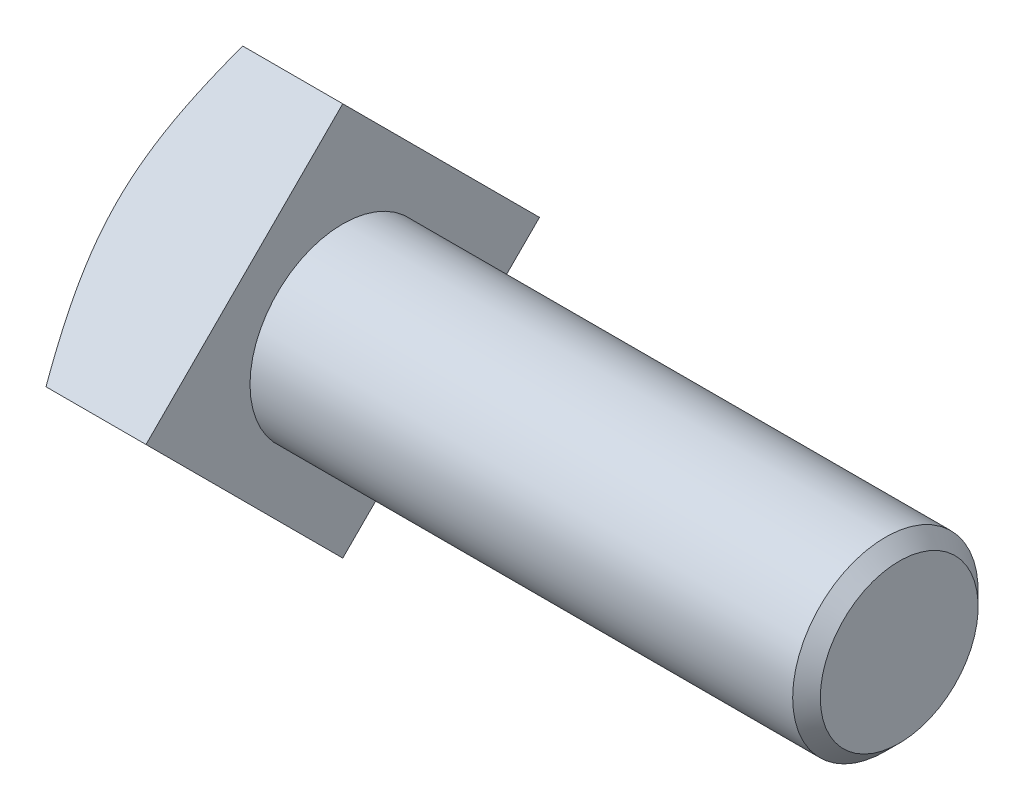
SolidWorks part; units mm, degrees
extrude "BaseHead" add sketch "Sketch1" along normal blind 17.3736
sketch "Sketch1" plane through (0, 0, 0) normal (1, 0, 0) x (0, 0.7071, -0.7071)
  line L0 (19.05, -19.05) -> (-19.05, -19.05)
  line L1 (19.05, -19.05) -> (19.05, 19.05)
  line L2 (-19.05, 19.05) -> (19.05, 19.05)
  line L3 (-19.05, 19.05) -> (-19.05, -19.05)
  dimension "Width_flats" = 38.1
  dimension "D1" = 19.05
  dimension "D2" = 38.1
  dimension "D3" = 19.05
revolve "HeadChamfer" cut sketch "Sketch3" angle 360 about L5 other way angle 60
sketch "Sketch3" plane through (0, 0, 0) normal (0, 0, 1) x (1, 0, 0)
  line L0 (0, 19.05) -> (-12.7, 19.05)
  line L1 (0, 0) -> (0, 26.9408) construction
  line L2 (0, 19.05) -> (15.5237, 52.3408)
  line L3 (15.5237, 52.3408) -> (-12.7, 52.3408)
  line L4 (-12.7, 52.3408) -> (-12.7, 19.05)
  line L5 (0, 0) -> (31.75, 0) construction
  line L6 (17.3736, 26.9408) -> (0, 26.9408) construction
  dimension "D1" = 19.05
  dimension "D2" = 25.4
  dimension "D4" = 12.7
ref_plane "Plane1" through (0, 0, 0) normal (0, 0, 1) x (1, 0, 0)
ref_plane "Plane2" through (0, 0, 0) normal (0, 1, 0) x (1, 0, 0)
ref_plane "Plane3" through (0, 0, 0) normal (1, 0, 0) x (0, 0, -1)
sketch "BodySke" plane through (0, 0, 0) normal (0, 0, 1) x (1, 0, 0)
  line L0 (17.3736, 0) -> (17.3736, 12.7)
  line L1 (17.3736, 12.7) -> (91.6813, 12.7)
  line L2 (91.6813, 12.7) -> (93.5736, 10.8077)
  line L3 (93.5736, 10.8077) -> (93.5736, 0)
  line L4 (93.5736, 0) -> (17.3736, 0)
  line L5 (17.3736, 0) -> (17.3736, 26.9408) construction
  line L6 (0, 0) -> (38.1, 0) construction
  line L7 (91.6813, -12.7) -> (93.5736, -10.8077) construction
  line L8 (19.4818, 15.875) -> (19.4818, -6.35) construction
  line L9 (61.8236, 19.05) -> (61.8236, -6.35) construction
  dimension "Diameter" = 25.4
revolve "Body" add sketch "BodySke" angle 360 about L6
cosmetic thread "ThreadCosmetic" [suppressed] parameters "Thread_length"=31.75, "Thread_minor"=21.6154
fillet "HeadFillet" [suppressed]
sketch "ThdSchSke" plane through (0, 0, 0) normal (0, 0, 1) x (1, 0, 0)
  line L0 (61.8236, -10.8077) -> (60.4986, -12.7)
  line L1 (61.8236, -10.8077) -> (63.1486, -12.7)
  line L2 (63.1486, -12.7) -> (63.1486, -15.875)
  line L3 (-3.175, 0) -> (5.1513, 0) construction
  line L4 (0, 13.4704) -> (0, -13.4704) construction
  line L5 (63.1486, -15.875) -> (60.4986, -15.875)
  line L6 (60.4986, -15.875) -> (60.4986, -12.7)
  dimension "Thread_minor" = 21.6154
  dimension "Diameter" = 25.4
  dimension "Start" = 61.8236
revolve "ThreadSchematic" [suppressed] cut sketch "ThdSchSke" angle 360 about L3
pattern_linear "ThdSchPat" [suppressed]
equation "\"D1@Sketch1\" = \"Width_flats@Sketch1\" / 2"
equation "\"D2@Sketch1\" = \"Width_flats@Sketch1\""
equation "\"D3@Sketch1\" = \"D1@Sketch1\""
equation "\"D1@Sketch3\" = \"Width_flats@Sketch1\"/2"
equation "\"Thread_minor@ThreadCosmetic\" = \"Minor_dia@BodySke\""
equation "\"Thread_length@ThreadCosmetic\" = ((sgn( (\"Length@BodySke\" - \"Advance@BodySke\" ) - \"Thread_nom@BodySke\" )-1)*( (\"Length@BodySke\" - \"Advance@BodySke\" ) - \"Thread_nom@BodySke\" ))/-2+ \"Thread_nom@BodySke\""
equation "\"Thread_minor@ThdSchSke\" = \"Minor_dia@BodySke\""
equation "\"Diameter@ThdSchSke\" = \"Diameter@BodySke\""
equation "\"Overcut@ThdSchSke\" = \"Diameter@BodySke\" * 1.25"
equation "\"Start@ThdSchSke\" = \"Head_ht@BaseHead\" + \"Length@BodySke\" - \"Thread_length@ThreadCosmetic\"  '---Non-countersunk---"
equation "\"Num_threads@ThdSchPat\" = int( \"Thread_length@ThreadCosmetic\" / \"Advance@BodySke\" + 0.999 )  + 1"
equation "\"Advance@ThdSchPat\" = \"Thread_length@ThreadCosmetic\" /  (\"Num_threads@ThdSchPat\" - 1) 'relax it"
equation "\"Num_threads@ThdSchPat\" = \"Num_threads@ThdSchPat\" - sgn( \"Num_threads@ThdSchPat\" - 1) '---chamfered tips only---"
